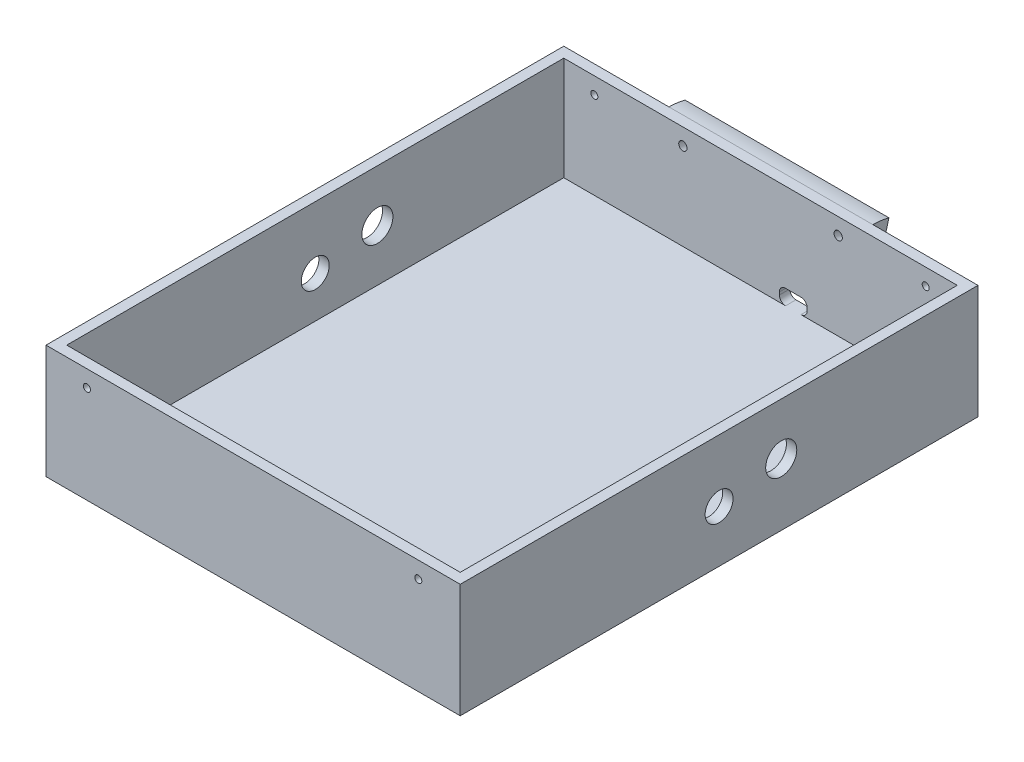
SolidWorks part; units mm, degrees
ref_plane "Front Plane" through (0, 0, 0) normal (0, 0, 1) x (1, 0, 0)
ref_plane "Top Plane" through (0, 0, 0) normal (0, 1, 0) x (1, 0, 0)
ref_plane "Right Plane" through (0, 0, 0) normal (1, 0, 0) x (0, 0, -1)
sketch "Sketch1" plane through (0, 0, 0) normal (0, 0, 1) x (1, 0, 0)
  line L0 (0, 50) -> (0, 0) construction
  line L1 (-95, 0) -> (95, 0)
  line L2 (-95, 0) -> (-95, 50)
  line L3 (-95, 50) -> (95, 50)
  line L4 (95, 0) -> (95, 50)
  dimension "D1" = 190
  dimension "D2" = 50
extrude "Boss-Extrude1" add sketch "Sketch1" along normal mid plane 240
shell "Shell1" thickness 5 removed face at (0, 50, 0) outward yes
sketch "Sketch3" plane through (100, 0, 0) normal (1, 0, 0) x (0, 0, -1)
  line L0 (-125, -5) -> (125, -5) construction
  line L1 (-15, -5) -> (15, -5)
  line L2 (-15, -5) -> (-15, 30)
  line L3 (-15, 30) -> (15, 30) construction
  line L4 (15, -5) -> (15, 30)
  line L5 (0, 30) -> (0, 20) construction
  line L6 (9.0631, 24.2262) -> (-0.618, 44.9873)
  line L7 (-15, 28.5056) -> (-9.0631, 15.7738)
  circle A0 centre (0, 20) radius 6.75
  arc A1 (-15, 30) -> (15, 30) centre (0, 30) cw
  circle A2 centre (0, 20) radius 10
  dimension "D2" = 13.5
  dimension "D5" = 20
  dimension "D1" = 25
  dimension "D3" = 30
  dimension "D4" = 10
  dimension "D6" = 25
extrude "Cut-Extrude2" cut sketch "Sketch3" against normal through all both and the other way through all contours A0 region at (100, 20, 0)
hole_wizard "M3 Clearance Hole1" positions "Sketch4" profile "Sketch5" hole size "M3" standard "ANSI Metric" end condition through all
sketch "Sketch4" plane through (0, 0, 125) normal (0, 0, 1) x (1, 0, 0)
  point P0 (-80.25, 42)
  point P1 (79.75, 42)
sketch "Sketch5" plane through (-80.25, 42, 125) normal (1, 0, 0) x (0, -1, 0)
  line L0 (0, 0) -> (0, 250)
  line L1 (0, 250) -> (1.7, 250)
  line L2 (1.7, 250) -> (1.7, 0)
  line L3 (1.7, 0) -> (0, 0)
  line L4 (0, -6.35) -> (0, 107.95) construction
  dimension "Thru Hole Dia." = 3.4
  dimension "Thru Hole Depth" = 250
sketch "Sketch8" plane through (0, 0, 0) normal (1, 0, 0) x (0, 0, -1)
  circle A0 centre (30, 25) radius 7.5
  dimension "D1" = 15
  dimension "D2" = 25
  dimension "D3" = 30
extrude "Cut-Extrude4" cut sketch "Sketch8" against normal through all both and the other way through all
sketch "Sketch10" plane through (0, 0, -125) normal (0, 0, -1) x (-1, 0, 0)
  line L0 (-100, -5) -> (-100, 50) construction
  line L5 (-22.5, 7.3) -> (-9.1, 7.3)
  line L6 (-22.5, 7.3) -> (-22.5, 0)
  line L7 (-22.5, 0) -> (-9.1, 0)
  line L8 (-9.1, 7.3) -> (-9.1, 0)
  line L9 (100, -5) -> (-100, -5) construction
  point P6 (-15.8, 0)
  dimension "D2" = 7.3
  dimension "D1" = 13.4
  dimension "D3" = 77.5
  dimension "D4" = 5
extrude "Cut-Extrude6" cut sketch "Sketch10" against normal up to surface (5 mm away) up to face at (-81.95, 42, -120)
fillet "Fillet1" radius 3 4 edges at (9.1, 0, -122.5) (22.5, 0, -122.5) (9.1, 7.3, -122.5) (22.5, 7.3, -122.5)
sketch "Sketch11" plane through (0, 0, -125) normal (0, 0, -1) x (-1, 0, 0)
  line L0 (-100, 50) -> (100, 50) construction
  line L1 (-49.2173, 20) -> (49.2173, 20)
  line L2 (-49.2173, 20) -> (-49.2173, 50)
  line L3 (-49.2173, 50) -> (49.2173, 50)
  line L4 (49.2173, 20) -> (49.2173, 50)
  line L5 (0, 0) -> (0, 50) construction
  dimension "D1" = 30
revolve "Revolve1" add sketch "Sketch11" angle 15 about L1
sketch "Sketch12" plane through (0, -29.9103, -111.6266) normal (0, -0.2588, -0.9659) x (-1, 0, 0)
  line L0 (0, 0) -> (0, 91.0316) construction
  line L1 (49.2173, 81.6709) -> (-49.2173, 81.6709) construction
  circle A0 centre (-37.5, 71.6709) radius 2
  dimension "D3" = 4
  dimension "D1" = 37.5
  dimension "D2" = 10
extrude "Cut-Extrude7" cut sketch "Sketch12" against normal up to surface (11.0713 mm away) up to face at (-81.95, 42, -120)
mirror "Mirror2" about plane through (0, 0, 0) normal (1, 0, 0) of "Cut-Extrude7"
